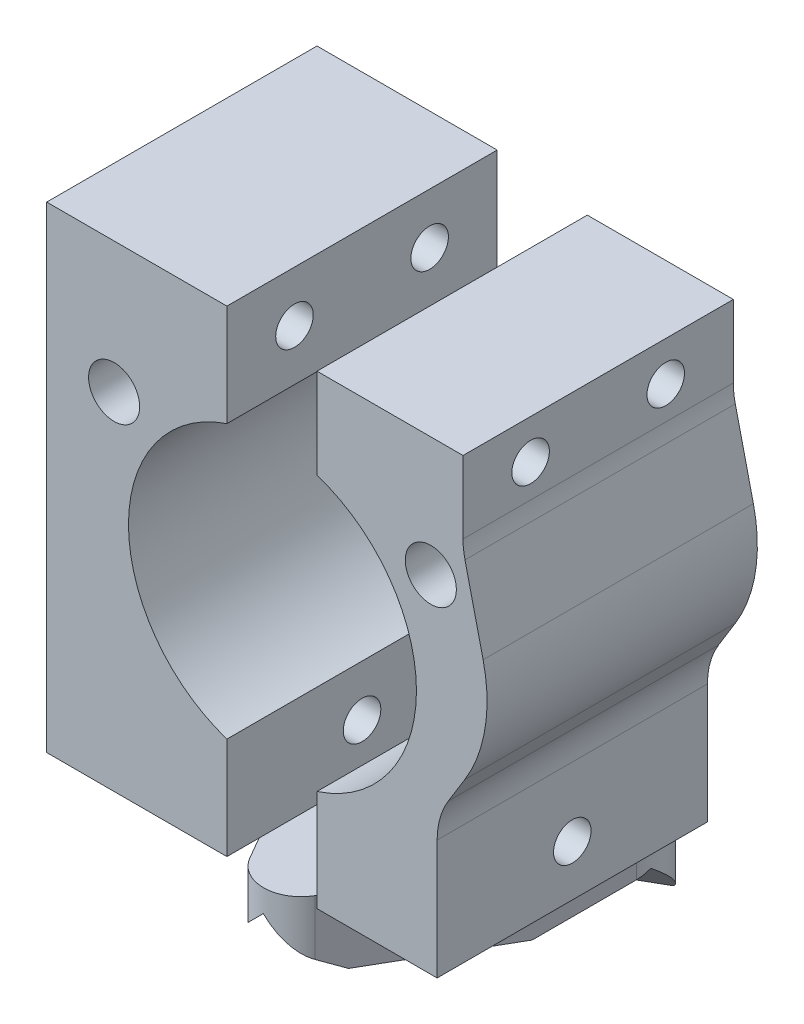
SolidWorks part; units mm, degrees
note: '?' marks a value the reader was unsure of.
material "Plain Carbon Steel"
ref_plane "Front Plane" through (0, 0, 0) normal (0, 0, 1) x (1, 0, 0)
ref_plane "Top Plane" through (0, 0, 0) normal (0, 1, 0) x (1, 0, 0)
ref_plane "Right Plane" through (0, 0, 0) normal (1, 0, 0) x (0, 0, -1)
sketch "Sketch1" plane through (0, 0, 0) normal (0, 1, 0) x (1, 0, 0)
  line L0 (0, 4.75) -> (0, -4.75) construction
  line L1 (3, 3.6827) -> (3, -3.6827)
  line L2 (-3, 3.6827) -> (-3, -3.6827)
  line L3 (-9.9899, 3.2677) -> (-8.4595, 0.617)
  line L4 (2.1776, -10.307) -> (8.4783, 0.6062)
  line L5 (7.8498, 7.0177) -> (4.7641, 7.0177)
  line L6 (-6.6271, -3.8261) -> (9.3066, 5.3731) construction
  line L7 (0, 7.0177) -> (0, -11.8662) construction
  line L8 (4.3301, -2.5) -> (-9.863, 5.6944) construction
  line L9 (-3.6955, -7.6347) -> (-2.1526, -10.307)
  line L10 (-12.155, 7.0177) -> (-2.961, 7.0177) construction
  line L11 (12.155, 7.0177) -> (0, -14.0354) construction
  line L12 (0, -14.0354) -> (-12.155, 7.0177) construction
  line L13 (-12.155, 7.0177) -> (12.155, 7.0177) construction
  line L14 (8.4783, 0.6062) -> (10.0149, 3.2677)
  line L15 (-4.7641, 7.0177) -> (-7.8249, 7.0177)
  line L16 (2.961, 7.0177) -> (12.155, 7.0177) construction
  line L17 (-4.7641, 7.0177) -> (4.7641, 7.0177)
  line L18 (-3.6955, -7.6347) -> (-8.4595, 0.617)
  circle A2 centre (0, 0) radius 7.5 construction
  arc A5 (-9.9899, 3.2677) -> (-7.8249, 7.0177) centre (-7.8249, 4.5177) cw
  arc A6 (2.1776, -10.307) -> (-2.1526, -10.307) centre (0.0125, -9.057) cw
  arc A7 (7.8498, 7.0177) -> (10.0149, 3.2677) centre (7.8498, 4.5177) cw
  point P16 (-6.4952, -3.75)
  point P17 (0, 7.5)
  point P18 (6.4952, -3.75)
  point P23 (0, 0)
  dimension "D6" = 2.5
  dimension "D7" = 15
  dimension "D2" = 3
  dimension "D3" = 120
  dimension "D4" = 240
ref_plane "GroundPlane" through (0, 4.5, 0) normal (0, 1, 0) x (-1, 0, 0)
sketch "Sketch2" plane through (0, 4.5, 0) normal (0, 1, 0) x (-1, 0, 0)
  line L0 (0, 7.5) -> (6.4952, -3.75) construction
  line L1 (0, 7.5) -> (0, -7.5) construction
  line L2 (0, 12.7) -> (0, -12.7) construction
  line L3 (0, 7.5) -> (-6.4952, -3.75) construction
  line L4 (-9.2393, -11.2686) -> (9.8107, -11.2686) construction
  line L5 (-9.2393, -11.2686) -> (-9.2393, -30.3186) construction
  line L6 (-9.2393, -30.3186) -> (9.8107, -30.3186) construction
  line L7 (9.8107, -11.2686) -> (9.8107, -30.3186) construction
  line L8 (-6.4952, -3.75) -> (6.4952, -3.75) construction
  line L9 (0, -7.5) -> (6.4952, 3.75) construction
  line L10 (6.4952, 3.75) -> (-6.4952, 3.75) construction
  line L11 (-6.4952, 3.75) -> (0, -7.5) construction
  line L12 (3, -7.0177) -> (3, 10.9823)
  line L13 (3, -7.0177) -> (15, -7.0177)
  line L14 (3, 10.9823) -> (15, 10.9823)
  line L15 (15, 10.9823) -> (15, -7.0177)
  line L16 (-3, -7.0177) -> (-3, 10.9823)
  line L17 (-3, -7.0177) -> (-15, -7.0177)
  line L18 (-3, 10.9823) -> (-15, 10.9823)
  line L19 (-15, 10.9823) -> (-15, -7.0177)
  line L20 (4.7641, -7.0177) -> (-4.7641, -7.0177) construction
  circle A0 centre (0, 0) radius 7.5 construction
  dimension "D1" = 15
  dimension "D2" = 30
  dimension "D3" = 25.4
  dimension "D4" = 19.05
  dimension "D5" = 19.05
  dimension "D6" = 30
  dimension "D7" = 30
  dimension "D8" = 3
  dimension "D9" = 18
  dimension "D10" = 12
ref_plane "TopPlane" through (0, 36.25, 0) normal (0, 1, 0) x (-1, 0, 0)
extrude "Extrude1" add sketch "Sketch2" along normal blind 31.75
sketch "Sketch4" plane through (0, 0, 10.9823) normal (0, 0, 1) x (1, 0, 0)
  line L0 (-14.9586, 36.25) -> (15.0262, 4.5) construction
  line L1 (16.5, 36.25) -> (-16.5, 36.25) construction
  line L2 (16.5, 4.5) -> (-16.5, 4.5) construction
  line L3 (15.0262, 36.25) -> (-14.9586, 4.5) construction
  circle A0 centre (0.0338, 20.375) radius 9.5885
  point P8 (0.0338, 20.375)
  dimension "D1" = 19.177
extrude "Magnet Cavity" cut sketch "Sketch4" against normal through all
sketch "Sketch6" plane through (15, 0, 0) normal (1, 0, 0) x (0, 0, -1)
  line L0 (-10.9823, 36.25) -> (-10.9823, 4.5) construction
  line L1 (-10.9823, 20.375) -> (7.0177, 20.375) construction
  line L2 (7.0177, 36.25) -> (7.0177, 4.5) construction
  line L3 (-1.9823, 36.25) -> (-1.9823, 4.5) construction
  line L4 (-10.9823, 36.25) -> (7.0177, 36.25) construction
  line L5 (-10.9823, 4.5) -> (7.0177, 4.5) construction
  line L6 (-1.9823, 36.25) -> (-10.9823, 29.4932) construction
  point P12 (-6.4823, 32.8716)
  point P15 (2.5177, 32.8716)
  point P16 (2.5177, 7.8784)
  point P17 (-6.4823, 7.8784)
  point P18 (-1.9823, 32.8716)
  point P19 (-1.9823, 7.8784)
sketch "Mount Hole circle" plane through (0, 0, 10.9823) normal (0, 0, 1) x (1, 0, 0)
  line L0 (0.0338, 20.375) -> (0.0338, 33.125) construction
  line L1 (0.0338, 20.375) -> (10.5793, 27.5412) construction
  line L2 (0.0338, 20.375) -> (-10.5117, 27.5412) construction
  circle A0 centre (0.0338, 20.375) radius 12.75 construction
  dimension "D1" = 25.5
  dimension "D2" = 55.802
sketch "Sketch14" plane through (0, 4.5, 0) normal (0, 1, 0) x (-1, 0, 0)
  point P0 (6.4952, 3.75)
  point P1 (-6.4952, 3.75)
  point P3 (0, -7.5)
sketch "Sketch16" plane through (0, 4.5, 0) normal (0, 1, 0) x (-1, 0, 0)
  point P0 (6.4952, 3.75)
  point P1 (-6.4952, 3.75)
  point P3 (0, -7.5)
hole_wizard "M3x0.5 Tapped Hole1" positions "3DSketch3" profile "Sketch18" tap size "M3x0.5" standard "Ansi Metric" end condition through all
sketch3d "3DSketch3"
  point P0 (15, 32.8716, 6.4823)
  point P3 (15, 32.8716, -2.5177)
  point P6 (15, 7.8784, 1.9823)
sketch "Sketch18" plane through (15, 32.8716, 6.4823) normal (0, 1, 0) x (0, 0, -1)
  line L0 (0, 0) -> (0, 30)
  line L1 (0, 30) -> (1.25, 30)
  line L2 (1.25, 30) -> (1.25, 0)
  line L5 (1.25, 0) -> (0, 0)
  line L11 (0, -6.35) -> (0, 107.95) construction
  dimension "Thru Tap Drill Dia." = 2.5
  dimension "Thru Tap Drill Depth" = 30
cosmetic thread "Hole Thread6" parameters "D2"=3
cosmetic thread "Hole Thread7" parameters "D2"=3
cosmetic thread "Hole Thread8" parameters "D2"=3
hole_wizard "M3 Clearance Hole1" positions "3DSketch9" profile "Sketch24" hole size "M3" standard "Ansi Metric"
sketch3d "3DSketch9"
  point P0 (-10.5117, 27.5412, 10.9823)
  point P3 (10.5793, 27.5412, 10.9823)
sketch "Sketch24" plane through (-10.5117, 27.5412, 10.9823) normal (1, 0, 0) x (0, -1, 0)
  line L0 (0, 0) -> (0, 19.0215)
  line L1 (0, 19.0215) -> (1.7, 18)
  line L2 (1.7, 18) -> (1.7, 0)
  line L5 (1.7, 0) -> (0, 0)
  line L10 (0, 19.0215) -> (-1.7, 18) construction
  line L11 (0, -6.35) -> (0, 107.95) construction
  dimension "Hole Dia." = 3.4
  dimension "Hole Depth" = 18
  dimension "Drill Angle" = 118
sketch "Trim Sketch" plane through (0, 0, 10.9823) normal (0, 0, 1) x (1, 0, 0)
  line L0 (11, 4.5) -> (11, 12.4564)
  line L2 (11.741, 15.0757) -> (12.843, 16.8677)
  line L3 (15, 36.25) -> (15, 4.5) construction
  line L4 (14.062, 24.3842) -> (12.8557, 29.5406)
  line L5 (12.7242, 30.6796) -> (12.7242, 35.4973)
  line L6 (12.7242, 35.4973) -> (3, 35.4973)
  line L7 (3, 36.25) -> (3, 29.4932) construction
  line L8 (0.0338, 33.125) -> (0, 0) construction
  line L9 (-10.9908, 4.5224) -> (-10.9746, 12.4788)
  line L10 (-11.7102, 15.0996) -> (-12.8086, 16.8938)
  line L11 (-14.0123, 24.4129) -> (-12.7954, 29.5667)
  line L12 (-12.6616, 30.7055) -> (-12.6518, 35.5232)
  line L13 (-12.6518, 35.5232) -> (-3, 35.5232)
  line L14 (-3, 36.25) -> (-3, 29.4709) construction
  line L15 (3, 11.2568) -> (3, 4.5) construction
  circle A0 centre (0.0338, 20.375) radius 12.75 construction
  arc A1 (12.8557, 29.5406) -> (12.7242, 30.6796) centre (17.7242, 30.6796) cw
  arc A2 (12.843, 16.8677) -> (14.062, 24.3842) centre (4.3249, 22.1062) ccw
  arc A3 (11.741, 15.0757) -> (11, 12.4564) centre (16, 12.4564) ccw
  arc A4 (-11.7102, 15.0996) -> (-10.9746, 12.4788) centre (-15.9746, 12.489) cw
  arc A5 (-12.8086, 16.8938) -> (-14.0123, 24.4129) centre (-4.2799, 22.115) cw
  arc A6 (-12.7954, 29.5667) -> (-12.6616, 30.7055) centre (-17.6616, 30.7157) ccw
  point P18 (15, 20.375)
  point P21 (11, 13.8708)
  line M2 (3, 36.25) -> (3, 29.4932)
  line M5 (3, 4.5) -> (15, 4.5)
  line M6 (15, 4.5) -> (15, 36.25)
  line M7 (15, 36.25) -> (3, 36.25)
  dimension "D1" = 5
  dimension "D2" = 10
  dimension "D3" = 5
  dimension "D4" = 8
extrude "Extrude3" cut sketch "Trim Sketch" along direction (0, 0, -1) on the side against the normal through all contours L2 A3 L0 L6 L5 A1 L4 A2 M5 M6 M7 M2
sketch "Sketch27" plane through (0, 0, 10.9823) normal (0, 0, 1) x (1, 0, 0)
  line L0 (-14.1566, 24.0762) -> (-12.771, 30.1568)
  line L1 (-15, 36.25) -> (-15, 4.5) construction
  line L2 (-12.646, 31.2677) -> (-12.646, 35.4975)
  line L3 (-12.646, 35.4975) -> (-3, 35.4975)
  line L4 (-3, 36.25) -> (-3, 29.4709) construction
  line L6 (-3, 9.4328) -> (-9, 9.4328) construction
  line L7 (-3, 11.2791) -> (-3, 4.5) construction
  line L8 (-13.1749, 17.0465) -> (-10.2317, 11.679)
  line L9 (-9, 6.871) -> (-9, 4.5)
  arc A0 (-12.771, 30.1568) -> (-12.646, 31.2677) centre (-17.646, 31.2677) ccw
  arc A1 (-13.1749, 17.0465) -> (-14.1566, 24.0762) centre (-4.4065, 21.8544) cw
  arc A2 (-9, 6.871) -> (-10.2317, 11.679) centre (-19, 6.871) ccw
  point P17 (-15, 20.375)
  dimension "D2" = 5
  dimension "D3" = 10
  dimension "D1" = 6
sketch "Sketch28" plane through (0, 36.25, 0) normal (0, 1, 0) x (1, 0, 0)
  line L0 (-3, 7.0177) -> (3, -10.9823) construction
  line L1 (3, 7.0177) -> (-3, -10.9823) construction
  point P7 (0, -1.9823)
ref_axis "Axis2" through (0, 36.25, 1.9823) along (0, -1, 0)?
extrude "Extrude5" add sketch "Sketch1" along normal up to surface (4.5 mm away) contours A6 L9 L18 L3 A5 L15 L17 L5 A7 L14 L4 up to face at (-9, 4.5, 1.9823)
sketch "Sketch29" plane through (0, 0, -7.0177) normal (0, 0, -1) x (-1, 0, 0)
  line L2 (0, 3) -> (-3, 0)
  line L3 (0, 3) -> (3, 0)
  line L4 (-7.8498, 0) -> (7.8249, 0) construction
  line L5 (0, 0) -> (0, 3) construction
  point P8 (0, 3)
  line M21 (-7.8498, 0) -> (7.8249, 0)
  dimension "D1" = 90
  dimension "D2" = 45
  dimension "D3" = 3
extrude "Extrude8" cut sketch "Sketch29" against normal through all from offset 8 contours L3 L2 M21 | L5 L3 M21
pattern_circular "CirPattern1" count 3 over 360 about axis through (0, 0, 1.9823) along (0, 1, 0) of "Extrude8"
